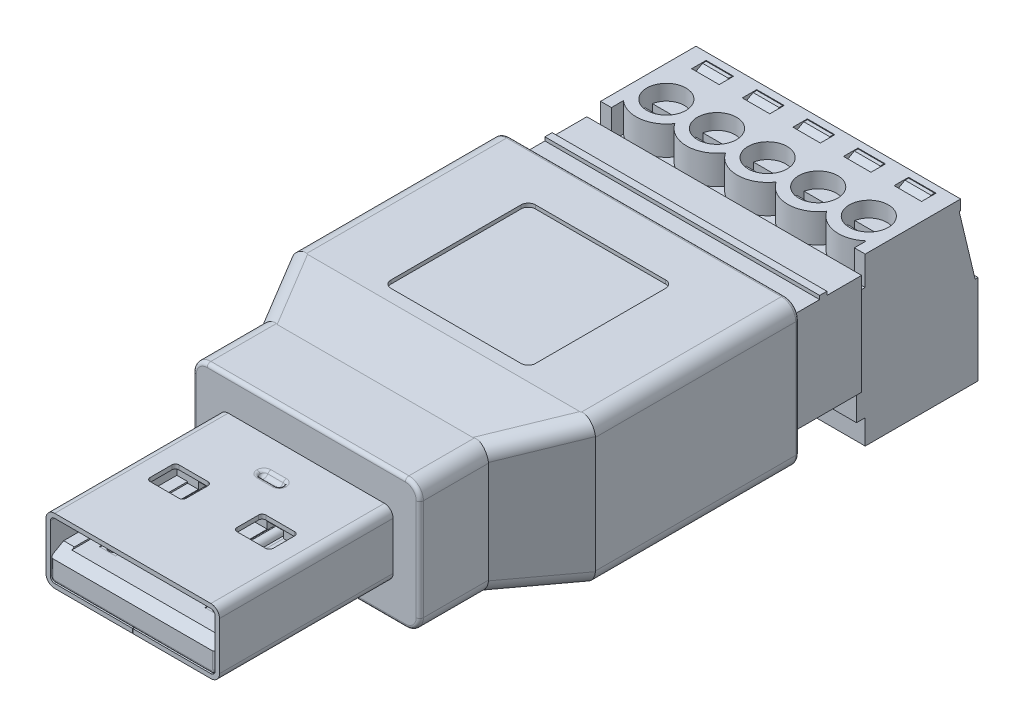
SolidWorks part; units mm, degrees
ref_plane "Front Plane" through (0, 0, 0) normal (0, 0, 1) x (1, 0, 0)
ref_plane "Top Plane" through (0, 0, 0) normal (0, 1, 0) x (1, 0, 0)
ref_plane "Right Plane" through (0, 0, 0) normal (1, 0, 0) x (0, 0, -1)
sketch "Sketch1" plane through (0, 0, 0) normal (1, 0, 0) x (0, 0, -1)
  line L0 (-24.65, 0) -> (24.65, 0) construction
  line L1 (-12.65, 4.5) -> (-12.65, -4.5) construction
  line L2 (10.95, 5) -> (10.95, -5) construction
  line L3 (10.95, 5) -> (-3.15, 5) construction
  line L4 (-12.65, 4.5) -> (-7.9, 4.5) construction
  line L5 (-7.9, 4.5) -> (-3.15, 5) construction
  line L6 (-24.65, 2.25) -> (-24.65, -2.25) construction
  line L7 (16.25, 3.5) -> (16.25, -3.5) construction
  line L8 (24.65, 4.3) -> (24.65, -7.2) construction
  line L9 (24.65, -7.2) -> (16.85, -7.2) construction
  line L10 (16.85, -7.2) -> (16.85, -5.5)
  line L11 (16.85, -5.5) -> (16.25, -5.5)
  line L12 (16.25, 2.3) -> (16.85, 2.3)
  line L13 (16.85, 2.3) -> (16.85, 4.3)
  line L14 (16.85, 4.3) -> (23.45, 4.3)
  line L15 (24.65, -1) -> (24.45, -1) construction
  line L16 (23.45, 4.3) -> (23.45, 3.6) construction
  line L17 (23.45, 3.6) -> (24.45, -1) construction
  point P3 (10.95, 0)
  point P4 (-12.65, 0)
  point P20 (24.65, 0.5781)
  dimension "USB Length" = 12
  dimension "Rear Connector Length" = 13.7
  dimension "USB Housing Length" = 23.6
  dimension "D1" = 9
  dimension "D2" = 10
  dimension "D3" = 4.75
  dimension "D4" = 9.5
  dimension "D5" = 4.5
  dimension "D6" = 7
  dimension "D7" = 5.3
  dimension "D8" = 11.5
  dimension "D9" = 0.8
  dimension "D11" = 37.3
  dimension "D12" = 7.8
  dimension "D13" = 1.7
  dimension "D10" = 2
  dimension "D14" = 6.6
  dimension "D15" = 7.7781
  dimension "D16" = 6.2
  dimension "D17" = 0.2
  dimension "D18" = 0.7
sketch "Sketch2" plane through (0, 0, 0) normal (0, 1, 0) x (1, 0, 0)
  line L0 (-10.5, 10.95) -> (10.5, 10.95)
  line L1 (-7.85, -12.65) -> (7.85, -12.65)
  line L2 (-7.85, -12.65) -> (-7.85, -7.9)
  line L3 (-7.85, -7.9) -> (-10.5, -3.15)
  line L4 (-10.5, -3.15) -> (-10.5, 10.95)
  line L5 (-6, -24.65) -> (6, -24.65)
  line L6 (-4.25, -17.7) -> (-4.25, -19.2)
  line L7 (-4, -17.45) -> (-2, -17.45)
  line L8 (-4, -19.45) -> (-2, -19.45)
  line L9 (-1.75, -17.7) -> (-1.75, -19.2)
  line L10 (0, -12.65) -> (0, -24.65) construction
  line L11 (0, -12.65) -> (0, -17.45) construction
  line L12 (-0.5, -15.05) -> (0.5, -15.05) construction
  line L13 (-0.5, -14.55) -> (0.5, -14.55)
  line L14 (-0.5, -15.55) -> (0.5, -15.55)
  line L15 (-9.5, 10.95) -> (-9.5, 16.25) construction
  line L16 (-9.5, 13.85) -> (-9.5, 13.35)
  line L17 (-9.5, 13.85) -> (9.5, 13.85)
  line L18 (-9.5, 13.35) -> (9.5, 13.35)
  line L19 (9.5, 13.85) -> (9.5, 13.35)
  line L20 (-9.15, 16.25) -> (-9.15, 24.65) construction
  line L21 (-9.15, 17.25) -> (9.15, 17.25) construction
  line L22 (0, 17.25) -> (0, 16.25) construction
  line L23 (0, -24.65) -> (0, 24.65) construction
  line L24 (-4.5, 7.7) -> (4.5, 7.7)
  line L25 (-5, 7.2) -> (-5, -1.8)
  line L26 (5, 7.2) -> (5, -1.8)
  line L27 (-4.5, -2.3) -> (4.5, -2.3)
  line L28 (-5.25, 0.8981) -> (-2.6598, -2.15) construction
  line L29 (-4.6785, 1.3838) -> (-2.0883, -1.6643) construction
  line L30 (-5.8215, 0.4124) -> (-3.2313, -2.6357) construction
  line L31 (-10.5, -3.15) -> (10.5, -3.15) construction
  line L32 (-7.5, 8.95) -> (7.5, 8.95) construction
  line L33 (-7.5, 8.95) -> (-7.5, -3.15) construction
  line L34 (-6.75, 8.2) -> (2.0451, -2.15) construction
  line L35 (-6.1785, 8.6857) -> (2.6166, -1.6643) construction
  line L36 (-7.3215, 7.7143) -> (1.4736, -2.6357) construction
  line L37 (7.5, 8.95) -> (7.5, -3.15) construction
  line L38 (-2.0451, 8.2) -> (6.75, -2.15) construction
  line L39 (-1.4736, 8.6857) -> (7.3215, -1.6643) construction
  line L40 (-2.6166, 7.7143) -> (6.1785, -2.6357) construction
  line L41 (2.6598, 8.2) -> (5.25, 5.1519) construction
  line L42 (3.2313, 8.6857) -> (5.8215, 5.6376) construction
  line L43 (2.0883, 7.7143) -> (4.6785, 4.6662) construction
  line L44 (-3.3834, -0.1403) -> (-1.7944, 1.21) construction
  line L45 (-1.7809, 3.5107) -> (-0.1919, 4.861) construction
  line L46 (3.3834, 6.1903) -> (1.7944, 4.84) construction
  line L47 (-3.65, -22.3) -> (-3.65, -13) construction
  line L48 (-4, -22.3) -> (-4, -13)
  line L49 (-3.3, -22.3) -> (-3.3, -13)
  line L50 (-1.11, -21.3) -> (-1.11, -13) construction
  line L51 (-1.46, -21.3) -> (-1.46, -13)
  line L52 (-0.76, -21.3) -> (-0.76, -13)
  arc A0 (-4.25, -19.2) -> (-4, -19.45) centre (-4, -19.2) ccw
  arc A1 (-4, -17.45) -> (-4.25, -17.7) centre (-4, -17.7) ccw
  arc A2 (-2, -17.45) -> (-1.75, -17.7) centre (-2, -17.7) cw
  arc A3 (-2, -19.45) -> (-1.75, -19.2) centre (-2, -19.2) ccw
  arc A4 (-0.5, -14.55) -> (-0.5, -15.55) centre (-0.5, -15.05) ccw
  arc A5 (0.5, -15.55) -> (0.5, -14.55) centre (0.5, -15.05) ccw
  circle A6 centre (-7, 19.25) radius 1.35
  circle A8 centre (-3.5, 19.25) radius 1.35
  circle A9 centre (0, 19.25) radius 1.35
  circle A10 centre (3.5, 19.25) radius 1.35
  circle A11 centre (7, 19.25) radius 1.35
  arc A12 (5, -1.8) -> (4.5, -2.3) centre (4.5, -1.8) cw
  arc A13 (-5, -1.8) -> (-4.5, -2.3) centre (-4.5, -1.8) ccw
  arc A14 (-5, 7.2) -> (-4.5, 7.7) centre (-4.5, 7.2) cw
  arc A15 (4.5, 7.7) -> (5, 7.2) centre (4.5, 7.2) cw
  arc A16 (-4.6785, 1.3838) -> (-5.8215, 0.4124) centre (-5.25, 0.8981) ccw construction
  arc A17 (-3.2313, -2.6357) -> (-2.0883, -1.6643) centre (-2.6598, -2.15) ccw construction
  arc A18 (-6.1785, 8.6857) -> (-7.3215, 7.7143) centre (-6.75, 8.2) ccw construction
  arc A19 (1.4736, -2.6357) -> (2.6166, -1.6643) centre (2.0451, -2.15) ccw construction
  arc A20 (-1.4736, 8.6857) -> (-2.6166, 7.7143) centre (-2.0451, 8.2) ccw construction
  arc A21 (6.1785, -2.6357) -> (7.3215, -1.6643) centre (6.75, -2.15) ccw construction
  arc A22 (3.2313, 8.6857) -> (2.0883, 7.7143) centre (2.6598, 8.2) ccw construction
  arc A23 (4.6785, 4.6662) -> (5.8215, 5.6376) centre (5.25, 5.1519) ccw construction
  arc A24 (-4, -22.3) -> (-3.3, -22.3) centre (-3.65, -22.3) ccw
  arc A25 (-3.3, -13) -> (-4, -13) centre (-3.65, -13) ccw
  arc A26 (-1.46, -21.3) -> (-0.76, -21.3) centre (-1.11, -21.3) ccw
  arc A27 (-0.76, -13) -> (-1.46, -13) centre (-1.11, -13) ccw
  point P5 (-3, -19.45)
  point P24 (-4.25, -17.45)
  point P27 (-1.75, -17.45)
  point P30 (0, -15.05)
  point P38 (-9.5, 13.6)
  point P39 (-9.5, 13.6)
  point P60 (0, 7.7)
  point P67 (-3.9549, -0.6259)
  point P76 (-5, -2.3)
  point P79 (-5, 7.7)
  point P88 (-2.3525, 3.025)
  point P92 (-3.3834, -0.1403)
  point P103 (2.3525, 3.025)
  point P108 (3.9549, 6.6759)
  point P121 (-3.65, -17.65)
  point P130 (-1.11, -17.15)
  dimension "D7" = 0.25
  dimension "D16" = 2.7
  dimension "D21" = 0.5
  dimension "D1" = 21
  dimension "D2" = 15.7
  dimension "D3" = 12
  dimension "D4" = 2.5
  dimension "D5" = 2
  dimension "D6" = 3.5
  dimension "D8" = 5.2
  dimension "D9" = 1
  dimension "D10" = 1
  dimension "D11" = 19
  dimension "D12" = 0.5
  dimension "D13" = 18.3
  dimension "D14" = 3
  dimension "D15" = 1
  dimension "D17" = 7
  dimension "D19" = 10
  dimension "D20" = 3.25
  dimension "D23" = 5.5
  dimension "D24" = 1.5
  dimension "D25" = 0.25
  dimension "D27" = 2
  dimension "D28" = 3
  dimension "D22" = 1
  dimension "D26" = 2.54
  dimension "D29" = 0.7
  dimension "D30" = 2.22
  dimension "D31" = 2
  dimension "D18" = 5
sketch "Sketch3" plane through (0, 0, 0) normal (0, 0, 1) x (1, 0, 0)
  line L0 (-8.25, -1.85) -> (-8.25, -5.85)
  line L1 (-8.25, -1.85) -> (-5.75, -1.85)
  line L2 (-8.25, -5.85) -> (-5.75, -5.85)
  line L3 (-5.75, -1.85) -> (-5.75, -5.85)
  line L4 (-7, -1.85) -> (-7, 0) construction
  dimension "D1" = 1.35
  dimension "D2" = 4
  dimension "D3" = 2.5
sketch "Sketch4" plane through (0, 0, 0) normal (0, 1, 0) x (1, 0, 0)
  line L0 (-10.5, 10.95) -> (10.5, 10.95) construction
  line L1 (-10.5, -3.15) -> (-10.5, 10.95) construction
  line L2 (-7.85, -7.9) -> (-10.5, -3.15) construction
  line L3 (-7.85, -12.65) -> (-7.85, -7.9) construction
  line L4 (-7.85, -12.65) -> (7.85, -12.65) construction
  line L5 (-10.5, 10.95) -> (0, 10.95)
  line L6 (-10.5, -3.15) -> (-10.5, 10.95)
  line L7 (-7.85, -7.9) -> (-10.5, -3.15)
  line L8 (-7.85, -12.65) -> (-7.85, -7.9)
  line L9 (-7.85, -12.65) -> (0, -12.65)
  line L10 (0, 10.95) -> (0, -12.65)
extrude "Boss-Extrude1" add sketch "Sketch4" against normal up to vertex (5 mm away) from vertex up to point (0, -5, -10.95) starting at point (0, 5, -10.95)
sketch "Sketch5" plane through (0, 0, 0) normal (1, 0, 0) x (0, 0, -1)
  line L0 (-12.65, 4.5) -> (-7.9, 4.5) construction
  line L1 (-7.9, 4.5) -> (-3.15, 5) construction
  line L2 (-12.65, 4.5) -> (-7.9, 4.5)
  line L3 (-7.9, 4.5) -> (-3.15, 5)
  line L4 (-12.65, 4.5) -> (-12.65, -4.5)
  line L5 (-12.65, 0) -> (-17.4, 0) construction
  line L6 (-7.9, -4.5) -> (-3.15, -5)
  line L7 (-12.65, -4.5) -> (-7.9, -4.5)
extrude "Cut-Extrude1" cut sketch "Sketch5" against normal through all and the other way through all flip side to cut
sketch "Sketch7" plane through (0, 0, 0) normal (1, 0, 0) x (0, 0, -1)
  line L0 (10.95, 3.5) -> (13.35, 3.5)
  line L1 (10.95, 3.5) -> (10.95, -3.5)
  line L2 (16.25, 3.5) -> (16.25, -3.5)
  line L3 (10.95, -3.5) -> (16.25, -3.5)
  line L4 (16.25, 3.5) -> (16.25, -3.5) construction
  line L5 (10.95, 5) -> (10.95, -5) construction
  line L6 (13.35, 3.5) -> (13.35, 3.75)
  line L7 (13.35, 3.75) -> (13.85, 3.75)
  line L8 (13.85, 3.75) -> (13.85, 3.5)
  line L9 (13.85, 3.5) -> (16.25, 3.5)
  dimension "D1" = 0.25
extrude "Boss-Extrude2" add sketch "Sketch7" against normal up to vertex (9.5 mm away) separate body up to point (-9.5, 0, -10.95)
sketch "Sketch8" plane through (0, 0, 0) normal (1, 0, 0) x (0, 0, -1)
  line L0 (16.85, -5.5) -> (16.25, -5.5) construction
  line L1 (16.85, -7.2) -> (16.85, -5.5) construction
  line L2 (24.65, -7.2) -> (16.85, -7.2) construction
  line L3 (24.65, 4.3) -> (24.65, -7.2) construction
  line L4 (24.65, -1) -> (24.45, -1) construction
  line L6 (23.45, 4.3) -> (23.45, 3.6) construction
  line L7 (16.85, 4.3) -> (23.45, 4.3) construction
  line L8 (16.85, 2.3) -> (16.85, 4.3) construction
  line L9 (16.25, 2.3) -> (16.85, 2.3) construction
  line L10 (16.85, -5.5) -> (16.25, -5.5)
  line L11 (16.85, -7.2) -> (16.85, -5.5)
  line L12 (24.65, -7.2) -> (16.85, -7.2)
  line L13 (24.65, -1) -> (24.65, -7.2)
  line L14 (24.65, -1) -> (24.45, -1)
  line L16 (23.45, 4.3) -> (23.45, 3.6)
  line L17 (16.85, 4.3) -> (23.45, 4.3)
  line L18 (16.85, 2.3) -> (16.85, 4.3)
  line L19 (16.25, 2.3) -> (16.85, 2.3)
  line L20 (16.25, 2.3) -> (16.25, -5.5)
  line L21 (23.45, 3.6) -> (23.35, 3.6)
  line L22 (23.35, 3.6) -> (24.45, -1)
  dimension "D1" = 0.1
extrude "Boss-Extrude3" add sketch "Sketch8" against normal up to vertex (9.15 mm away) separate body up to point (-9.15, 0, -24.65)
sketch "Sketch9" plane through (0, 4.3, 0) normal (0, 1, 0) x (1, 0, 0)
  line L0 (-7.95, 22.95) -> (-6.05, 22.95)
  line L1 (-7.95, 22.95) -> (-7.95, 21.95)
  line L2 (-6.05, 22.95) -> (-6.05, 21.95)
  line L3 (-7.95, 21.95) -> (-6.05, 21.95)
  line L4 (-9.15, 23.45) -> (0, 23.45) construction
  line L5 (-4.45, 22.95) -> (-4.45, 21.95)
  line L6 (-4.45, 22.95) -> (-2.55, 22.95)
  line L7 (-4.45, 21.95) -> (-2.55, 21.95)
  line L8 (-2.55, 22.95) -> (-2.55, 21.95)
  line L9 (-0.95, 22.95) -> (-0.95, 21.95)
  line L10 (-0.95, 22.95) -> (0.95, 22.95)
  line L11 (-0.95, 21.95) -> (0.95, 21.95)
  line L12 (0.95, 22.95) -> (0.95, 21.95)
  circle A0 centre (0, 19.25) radius 1.35 construction
  circle A1 centre (-3.5, 19.25) radius 1.35 construction
  circle A2 centre (-7, 19.25) radius 1.35 construction
  circle A3 centre (0, 19.25) radius 1.35
  circle A4 centre (-3.5, 19.25) radius 1.35
  circle A5 centre (-7, 19.25) radius 1.35
  point P15 (-7, 21.95)
  point P16 (-3.5, 21.95)
  point P23 (0, 21.95)
  dimension "D1" = 0.5
  dimension "D2" = 1
  dimension "D3" = 1.9
extrude "Cut-Extrude2" cut sketch "Sketch9" against normal up to surface (2 mm away) up to face at (-4.575, 2.3, -16.55)
sketch "Sketch10" plane through (0, 4.3, 0) normal (0, 1, 0) x (1, 0, 0)
  line L0 (-8.4, 17.6848) -> (-8.4, 16.85)
  line L1 (-9.15, 16.85) -> (0, 16.85) construction
  line L2 (-8.4, 16.85) -> (0, 16.85)
  line L3 (0, 16.85) -> (0, 17.15)
  line L4 (-9.15, 23.45) -> (-9.15, 16.85) construction
  arc A0 (-8.4, 17.6848) -> (-5.25, 18.0892) centre (-7, 19.25) ccw
  circle A1 centre (-7, 19.25) radius 1.35 construction
  arc A3 (-1.75, 18.0892) -> (0, 17.15) centre (0, 19.25) ccw
  arc A4 (-5.25, 18.0892) -> (-1.75, 18.0892) centre (-3.5, 19.25) ccw
  circle A5 centre (-3.5, 19.25) radius 1.35 construction
  dimension "D1" = 0.75
  dimension "D2" = 0.75
extrude "Cut-Extrude3" cut sketch "Sketch10" against normal up to surface (2 mm away) up to face at (-4.575, 2.3, -16.55)
sketch "Sketch12" plane through (0, 0, 0) normal (1, 0, 0) x (0, 0, -1)
  line L0 (22.9, 4.3) -> (22.9, 3.3)
  line L1 (22.9, 3.3) -> (22.95, 3.3)
  line L2 (22.95, 2.3) -> (22.95, 4.3) construction
  line L3 (22.95, 3.3) -> (22.95, 2.3)
  line L4 (22.95, 2.3) -> (21.95, 2.3)
  line L5 (21.95, 2.3) -> (21.95, 3.6)
  line L6 (21.95, 4.3) -> (21.95, 2.3) construction
  line L7 (21.95, 3.6) -> (22.2, 3.6)
  line L8 (22.2, 3.6) -> (22.2, 4.0402)
  line L9 (22.2, 4.0402) -> (22.65, 4.3)
  line L10 (22.65, 4.3) -> (22.9, 4.3)
  line L11 (21.95, 4.3) -> (20.6, 4.3) construction
  line L12 (23.45, 4.3) -> (22.95, 4.3) construction
  dimension "D1" = 0.05
  dimension "D2" = 0.7
  dimension "D3" = 60
  dimension "D4" = 0.25
  dimension "D5" = 0.25
extrude "Boss-Extrude4" add sketch "Sketch12" against normal up to surface (7.95 mm away) up to face at (-7.95, 3.3, -22.45)
sketch "Sketch13" plane through (0, 3.6, 0) normal (0, 1, 0) x (1, 0, 0)
  line L0 (-7.95, 22.95) -> (-7.95, 21.95)
  line L1 (-7.95, 22.95) -> (-7.9, 22.95)
  line L2 (-7.95, 21.95) -> (-7.9, 21.95)
  line L3 (-7.9, 22.95) -> (-7.9, 21.95)
  line L4 (-6.05, 22.95) -> (-6.05, 21.95)
  line L5 (-6.05, 22.95) -> (-6.1, 22.95)
  line L6 (-6.05, 21.95) -> (-6.1, 21.95)
  line L7 (-6.1, 22.95) -> (-6.1, 21.95)
  line L8 (-7.95, 22.95) -> (-7.95, 22.9) construction
  line L9 (-4.45, 22.95) -> (-4.45, 21.95)
  line L10 (-4.45, 22.95) -> (-4.4, 22.95)
  line L11 (-4.45, 21.95) -> (-4.4, 21.95)
  line L12 (-4.4, 22.95) -> (-4.4, 21.95)
  line L13 (-2.55, 21.95) -> (-2.55, 22.95)
  line L14 (-2.55, 21.95) -> (-2.6, 21.95)
  line L15 (-2.55, 22.95) -> (-2.6, 22.95)
  line L16 (-2.6, 21.95) -> (-2.6, 22.95)
  line L17 (-0.95, 22.95) -> (-0.95, 21.95)
  line L18 (-0.95, 22.95) -> (-0.9, 22.95)
  line L19 (-0.95, 21.95) -> (-0.9, 21.95)
  line L20 (-0.9, 22.95) -> (-0.9, 21.95)
extrude "Cut-Extrude4" cut sketch "Sketch13" along normal blind 10
sketch "Sketch15" plane through (0, 0, -24.65) normal (0, 0, -1) x (-1, 0, 0)
  line L0 (8.25, -1.85) -> (5.75, -1.85) construction
  line L1 (8.25, -1.85) -> (8.25, -5.85) construction
  line L2 (8.25, -5.85) -> (5.75, -5.85) construction
  line L3 (5.75, -1.85) -> (5.75, -5.85) construction
  line L4 (8.25, -1.85) -> (5.75, -1.85)
  line L5 (8.25, -1.85) -> (8.25, -5.85)
  line L6 (8.25, -5.85) -> (5.75, -5.85)
  line L7 (5.75, -1.85) -> (5.75, -5.85)
  line L8 (2.25, -1.85) -> (2.25, -5.85)
  line L9 (4.75, -1.85) -> (2.25, -1.85)
  line L10 (4.75, -1.85) -> (4.75, -5.85)
  line L11 (4.75, -5.85) -> (2.25, -5.85)
  line L12 (-1.25, -1.85) -> (-1.25, -5.85)
  line L13 (1.25, -1.85) -> (-1.25, -1.85)
  line L14 (1.25, -1.85) -> (1.25, -5.85)
  line L15 (1.25, -5.85) -> (-1.25, -5.85)
  line L19 (0, -1.85) -> (0, 4.3) construction
  dimension "D1" = 3
extrude "Cut-Extrude5" cut sketch "Sketch15" against normal blind 2
draft "Draft1" type of draft neutral plane draft angle 5 faces to draft 8 face at (-0.625, -5.85, -23.65) face at (-3.5, -5.85, -23.65) face at (-2.25, -3.85, -23.65) face at (-1.25, -3.85, -23.65) face at (-4.75, -3.85, -23.65) face at (-7, -5.85, -23.65) face at (-8.25, -3.85, -23.65) face at (-5.75, -3.85, -23.65) neutral plane through (-9.15, -1, -24.65) neutral plane normal (0, 0, -1) parameters "D1"=5
draft "Draft2" type of draft neutral plane draft angle 30 faces to draft 3 face at (-0.5813, -1.85, -23.65) face at (-3.5, -1.85, -23.65) face at (-7, -1.85, -23.65) neutral plane through (-9.15, -1, -24.65) neutral plane normal (0, 0, -1) parameters "D1"=30
sketch "Sketch16" plane through (0, 0, -22.65) normal (0, 0, -1) x (-1, 0, 0)
  line L4 (0, -7.2) -> (0, -5.85) construction
  line L12 (8.575, -6.175) -> (8.575, -2.5047)
  line L13 (8.575, -2.5047) -> (5.425, -2.5047)
  line L14 (5.425, -2.5047) -> (5.425, -6.175)
  line L15 (5.425, -6.175) -> (8.575, -6.175)
  line L16 (8.575, -6.175) -> (8.575, -2.5047)
  line L17 (8.575, -2.5047) -> (0, -2.5047)
  line L18 (0, -2.5047) -> (0, -6.175)
  line L19 (0, -6.175) -> (8.575, -6.175)
  dimension "D1" = 0.5
extrude "Cut-Extrude6" cut sketch "Sketch16" against normal blind 2
sketch "Sketch17" plane through (-8.575, 0, 0) normal (1, 0, 0) x (0, 0, -1)
  line L0 (22.65, -3.3047) -> (22.65, -2.5047)
  line L1 (22.65, -3.3047) -> (22.25, -3.3047)
  line L2 (22.65, -2.5047) -> (22.25, -2.5047)
  line L3 (22.25, -3.3047) -> (22.25, -2.5047)
  line L4 (22.65, -2.5047) -> (22.65, -3.0047) construction
  line L5 (20.65, -2.5047) -> (22.65, -2.5047) construction
  dimension "D1" = 0.4
  dimension "D2" = 0.3
extrude "Boss-Extrude5" add sketch "Sketch17" along normal up to surface (8.575 mm away) separate body up to face at (0, 0.2273, -21.3742)
sketch "Sketch18" plane through (0, -7.2, 0) normal (0, -1, 0) x (1, 0, 0)
  line L0 (-6.05, -24.05) -> (-7.95, -24.05)
  line L1 (-6.05, -24.05) -> (-6.05, -23.05)
  line L2 (-7.95, -24.05) -> (-7.95, -23.05)
  line L3 (-6.05, -23.05) -> (-7.95, -23.05)
  line L4 (-7.95, -22.95) -> (-7.95, -21.95) construction
  line L5 (-6.05, -21.95) -> (-6.05, -22.95) construction
  line L6 (-9.15, -24.65) -> (0, -24.65) construction
  line L7 (-2.55, -24.05) -> (-2.55, -23.05)
  line L8 (-2.55, -24.05) -> (-4.45, -24.05)
  line L9 (-2.55, -23.05) -> (-4.45, -23.05)
  line L10 (-4.45, -24.05) -> (-4.45, -23.05)
  line L11 (0.95, -24.05) -> (0.95, -23.05)
  line L12 (0.95, -24.05) -> (-0.95, -24.05)
  line L13 (0.95, -23.05) -> (-0.95, -23.05)
  line L14 (-0.95, -24.05) -> (-0.95, -23.05)
  line L15 (-3.5, -24.05) -> (-3.5, -24.65) construction
  line L16 (-4.75, -24.65) -> (-2.25, -24.65) construction
  dimension "D1" = 0.6
  dimension "D2" = 3
extrude "Cut-Extrude7" cut sketch "Sketch18" against normal blind 1
sketch "Sketch19" plane through (0, 0, 0) normal (1, 0, 0) x (0, 0, -1)
  line L0 (23.05, -6.7) -> (23.3335, -6.7)
  line L1 (23.05, -6.2) -> (23.05, -7.2) construction
  line L2 (23.3335, -6.7) -> (23.7665, -6.95)
  line L3 (23.7665, -6.95) -> (24.05, -6.95)
  line L4 (24.05, -7.2) -> (24.05, -6.2) construction
  line L5 (23.05, -7.2) -> (24.05, -7.2) construction
  line L6 (23.05, -6.7) -> (23.05, -6.2)
  line L7 (23.05, -6.2) -> (24.05, -6.2)
  line L8 (24.05, -6.2) -> (24.05, -6.95)
  dimension "D1" = 0.25
  dimension "D2" = 0.25
  dimension "D3" = 210
extrude "Boss-Extrude6" add sketch "Sketch19" against normal up to surface (7.95 mm away) up to face at (-7.95, -6.7, -23.55)
sketch "Sketch20" plane through (0, -6.7, 0) normal (0, -1, 0) x (1, 0, 0)
  line L0 (-7.95, -23.05) -> (-7.95, -24.05)
  line L1 (-7.95, -23.05) -> (-7.9, -23.05)
  line L2 (-7.95, -24.05) -> (-7.9, -24.05)
  line L3 (-7.9, -23.05) -> (-7.9, -24.05)
  line L4 (-6.05, -23.05) -> (-6.05, -24.05)
  line L5 (-6.05, -23.05) -> (-6.1, -23.05)
  line L6 (-6.05, -24.05) -> (-6.1, -24.05)
  line L7 (-6.1, -23.05) -> (-6.1, -24.05)
  line L8 (-4.45, -23.05) -> (-4.45, -24.05)
  line L9 (-4.45, -23.05) -> (-4.4, -23.05)
  line L10 (-4.45, -24.05) -> (-4.4, -24.05)
  line L11 (-4.4, -23.05) -> (-4.4, -24.05)
  line L12 (-2.55, -23.05) -> (-2.55, -24.05)
  line L13 (-2.55, -23.05) -> (-2.6, -23.05)
  line L14 (-2.55, -24.05) -> (-2.6, -24.05)
  line L15 (-2.6, -23.05) -> (-2.6, -24.05)
  line L16 (-0.95, -23.05) -> (-0.95, -24.05)
  line L17 (-0.95, -23.05) -> (-0.9, -23.05)
  line L18 (-0.95, -24.05) -> (-0.9, -24.05)
  line L19 (-0.9, -23.05) -> (-0.9, -24.05)
  line L20 (-7.9, -22.9) -> (-7.9, -22.65) construction
extrude "Cut-Extrude8" cut sketch "Sketch20" along normal blind 1 and the other way blind 0.5
sketch "Sketch21" plane through (0, -5.5, 0) normal (0, -1, 0) x (1, 0, 0)
  line L0 (-2.1, -16.25) -> (-2.1, -16.85)
  line L1 (-2.1, -16.25) -> (-1.4, -16.25)
  line L2 (-2.1, -16.85) -> (-1.4, -16.85)
  line L3 (-1.4, -16.25) -> (-1.4, -16.85)
  line L4 (-9.15, -16.25) -> (0, -16.25) construction
  line L5 (-9.15, -16.85) -> (0, -16.85) construction
  line L6 (-5.6, -16.25) -> (-5.6, -16.85)
  line L7 (-5.6, -16.25) -> (-4.9, -16.25)
  line L8 (-5.6, -16.85) -> (-4.9, -16.85)
  line L9 (-4.9, -16.25) -> (-4.9, -16.85)
  line L10 (-6.05, -23.05) -> (-4.45, -23.05) construction
  line L12 (-5.25, -16.85) -> (-5.25, -23.05) construction
  line L13 (-2.55, -23.05) -> (-0.95, -23.05) construction
  line L14 (-1.75, -16.85) -> (-1.75, -23.05) construction
  dimension "D1" = 0.7
extrude "Cut-Extrude9" cut sketch "Sketch21" against normal offset from surface (3 mm away) 1 up to face at (-4.75, -3.5, -13.6) offset beyond the face yes
sketch "Sketch23" plane through (0, 5, 0) normal (0, 1, 0) x (1, 0, 0)
  line L0 (-4.5, 7.7) -> (4.5, 7.7) construction
  line L1 (5, 7.2) -> (5, -1.8) construction
  line L2 (-4.5, -2.3) -> (4.5, -2.3) construction
  line L3 (-5, 7.2) -> (-5, -1.8) construction
  line L4 (-4.5, 7.7) -> (4.5, 7.7)
  line L5 (5, 7.2) -> (5, -1.8)
  line L6 (-4.5, -2.3) -> (4.5, -2.3)
  line L7 (-5, 7.2) -> (-5, -1.8)
  arc A0 (-4.5, 7.7) -> (-5, 7.2) centre (-4.5, 7.2) ccw construction
  arc A1 (5, 7.2) -> (4.5, 7.7) centre (4.5, 7.2) ccw construction
  arc A2 (4.5, -2.3) -> (5, -1.8) centre (4.5, -1.8) ccw construction
  arc A3 (-5, -1.8) -> (-4.5, -2.3) centre (-4.5, -1.8) ccw construction
  arc A4 (-4.5, 7.7) -> (-5, 7.2) centre (-4.5, 7.2) ccw
  arc A5 (5, 7.2) -> (4.5, 7.7) centre (4.5, 7.2) ccw
  arc A6 (4.5, -2.3) -> (5, -1.8) centre (4.5, -1.8) ccw
  arc A7 (-5, -1.8) -> (-4.5, -2.3) centre (-4.5, -1.8) ccw
extrude "Cut-Extrude10" cut sketch "Sketch23" against normal blind 0.25
fillet "Fillet1" radius 1 6 edges at (-7.85, -4.5, 10.275) (-9.175, -4.75, 5.525) (-10.5, -5, -3.9) (-10.5, 5, -3.9) (-9.175, 4.75, 5.525) (-7.85, 4.5, 10.275)
fillet "Fillet2" radius 0.25 10 edges at (-4.75, -5, -10.95) (-10.2071, -4.7071, -10.95) (-10.5, 0, -10.95) (-10.2071, 4.7071, -10.95) (-4.75, 5, -10.95) (-3.425, -4.5, 12.65) (-7.5571, -4.2071, 12.65) (-7.85, 0, 12.65) (-7.5571, 4.2071, 12.65) (-3.425, 4.5, 12.65)
sketch "Sketch24" plane through (0, 0, 12.65) normal (0, 0, 1) x (1, 0, 0)
  line L0 (5.4, 2.25) -> (-5.4, 2.25)
  line L1 (0, 2.25) -> (0, -2.25) construction
  line L2 (-6, 1.65) -> (-6, -1.65)
  line L3 (5.4, -2.25) -> (-5.4, -2.25)
  line L4 (0, -4.25) -> (0, 4.25) construction
  line L5 (6, 1.65) -> (6, -1.65)
  arc A0 (-6, -1.65) -> (-5.4, -2.25) centre (-5.4, -1.65) ccw
  arc A1 (-5.4, 2.25) -> (-6, 1.65) centre (-5.4, 1.65) ccw
  arc A2 (5.4, 2.25) -> (6, 1.65) centre (5.4, 1.65) cw
  arc A3 (6, -1.65) -> (5.4, -2.25) centre (5.4, -1.65) cw
  dimension "D1" = 0.6
extrude "Extrude-Thin1" add sketch "Sketch24" along normal up to vertex (12 mm away) separate body thin up to point (0, 0, 24.65) thin type one direction reverse wall 0.3
sketch "Sketch25" plane through (0, 2.25, 0) normal (0, -1, 0) x (-1, 0, 0)
  line L0 (-1.125, -15.05) -> (1.125, -15.05)
  line L1 (-1.125, -15.05) -> (-1.125, -15.056)
  line L2 (1.125, -15.05) -> (1.125, -15.056)
  line L3 (-0.531, -15.65) -> (0.531, -15.65)
  line L4 (1.75, -17.45) -> (1.75, -12.65) construction
  line L5 (4, -17.45) -> (2, -17.45) construction
  line L6 (1.75, -17.7) -> (1.75, -19.2) construction
  line L8 (5.4, -12.65) -> (-5.4, -12.65) construction
  arc A0 (1.125, -15.056) -> (0.531, -15.65) centre (0.531, -15.056) cw
  arc A1 (-1.125, -15.056) -> (-0.531, -15.65) centre (-0.531, -15.056) ccw
  point P7 (1.75, -15.05)
  point P8 (0, -15.05)
  dimension "D2" = 0.594
  dimension "D1" = 2.25
  dimension "D3" = 0.6
revolve "Revolve1" add sketch "Sketch25" angle 180 about L0 reverse direction yes
sketch "Sketch27" plane through (0, 2.25, 0) normal (0, 1, 0) x (1, 0, 0)
  line L0 (1.125, -15.05) -> (-1.125, -15.05) construction
  line L1 (0.8249, -15.05) -> (-0.8249, -15.05)
  line L8 (-0.531, -15.35) -> (0.531, -15.35)
  line L9 (-0.531, -15.35) -> (0.531, -15.35)
  arc A8 (-0.825, -15.056) -> (-0.531, -15.35) centre (-0.531, -15.056) ccw
  arc A9 (0.531, -15.35) -> (0.825, -15.056) centre (0.531, -15.056) ccw
  arc A10 (-0.8249, -15.05) -> (-0.531, -15.35) centre (-0.531, -15.056) ccw
  arc A11 (0.531, -15.35) -> (0.8249, -15.05) centre (0.531, -15.056) ccw
  dimension "D1" = 0.3
revolve "Cut-Revolve1" cut sketch "Sketch27" angle 360 about L1
fillet "Fillet3" radius 0.25 6 edges at (0, 2.25, 15.35) (0.741, 2.25, 15.2618) (-0.741, 2.25, 15.2618) (0.741, 2.25, 14.8382) (-0.741, 2.25, 14.8382) (0, 2.25, 14.75)
sketch "Sketch28" plane through (0, 2.25, 0) normal (0, 1, 0) x (1, 0, 0)
  line L0 (-4, -17.45) -> (-2, -17.45) construction
  line L1 (-4.25, -17.7) -> (-4.25, -19.2) construction
  line L2 (-4, -19.45) -> (-2, -19.45) construction
  line L3 (-1.75, -17.7) -> (-1.75, -19.2) construction
  line L4 (-4, -17.45) -> (-2, -17.45)
  line L5 (-4.25, -17.7) -> (-4.25, -19.2)
  line L6 (-4, -19.45) -> (-2, -19.45)
  line L7 (-1.75, -17.7) -> (-1.75, -19.2)
  line L8 (0, -24.65) -> (0, -19.45) construction
  line L9 (5.4, -24.65) -> (-5.4, -24.65) construction
  line L10 (1.75, -17.7) -> (1.75, -19.2)
  line L11 (4, -19.45) -> (2, -19.45)
  line L12 (4.25, -17.7) -> (4.25, -19.2)
  line L13 (4, -17.45) -> (2, -17.45)
  arc A0 (-1.75, -17.7) -> (-2, -17.45) centre (-2, -17.7) ccw construction
  arc A1 (-4, -17.45) -> (-4.25, -17.7) centre (-4, -17.7) ccw construction
  arc A2 (-4.25, -19.2) -> (-4, -19.45) centre (-4, -19.2) ccw construction
  arc A3 (-2, -19.45) -> (-1.75, -19.2) centre (-2, -19.2) ccw construction
  arc A4 (-1.75, -17.7) -> (-2, -17.45) centre (-2, -17.7) ccw
  arc A5 (-4, -17.45) -> (-4.25, -17.7) centre (-4, -17.7) ccw
  arc A6 (-4.25, -19.2) -> (-4, -19.45) centre (-4, -19.2) ccw
  arc A7 (-2, -19.45) -> (-1.75, -19.2) centre (-2, -19.2) ccw
  arc A8 (2, -19.45) -> (1.75, -19.2) centre (2, -19.2) cw
  arc A9 (4.25, -19.2) -> (4, -19.45) centre (4, -19.2) cw
  arc A10 (4, -17.45) -> (4.25, -17.7) centre (4, -17.7) cw
  arc A11 (1.75, -17.7) -> (2, -17.45) centre (2, -17.7) cw
extrude "Cut-Extrude12" cut sketch "Sketch28" against normal through all
sketch "Sketch30" plane through (0, -2.25, 0) normal (0, -1, 0) x (1, 0, 0)
  line L0 (1, 24.65) -> (1, 22.7364) construction
  line L1 (1.3355, 22.5015) -> (1.8827, 22.7006) construction
  line L2 (2.2182, 22.4657) -> (2.2182, 20.4657) construction
  line L3 (1.8827, 20.2308) -> (1.3355, 20.43) construction
  line L4 (1.3355, 14.0701) -> (1.8827, 14.2693) construction
  line L5 (2.2182, 14.0344) -> (2.2182, 12.0344) construction
  line L6 (1.8827, 11.7995) -> (1.3355, 11.9986) construction
  line L7 (1, 20.195) -> (1, 14.3051) construction
  line L8 (1, 11.7637) -> (1, 9.8501) construction
  line L9 (1, 14.3051) -> (1, 13.0344) construction
  line L10 (1, 13.0344) -> (1, 11.7637) construction
  line L11 (1, 13.0344) -> (2.2182, 13.0344) construction
  line L12 (0.5, 24.65) -> (0.5, 23.8393) construction
  line L13 (0, 11.7637) -> (0, 9.8501)
  line L14 (-0.8827, 11.7995) -> (-0.3355, 11.9986)
  line L15 (-1.2182, 14.0344) -> (-1.2182, 12.0344)
  line L16 (-5.4, 24.65) -> (5.4, 24.65) construction
  line L17 (-0.3355, 14.0701) -> (-0.8827, 14.2693)
  line L18 (0, 20.195) -> (0, 14.3051)
  line L19 (-0.8827, 20.2308) -> (-0.3355, 20.43)
  line L20 (-1.2182, 22.4657) -> (-1.2182, 20.4657)
  line L21 (-0.3355, 22.5015) -> (-0.8827, 22.7006)
  line L22 (0, 24.65) -> (0, 22.7364)
  arc A0 (1.3355, 14.0701) -> (1, 14.3051) centre (1.25, 14.3051) cw construction
  arc A1 (1.3355, 11.9986) -> (1, 11.7637) centre (1.25, 11.7637) ccw construction
  arc A2 (1.3355, 22.5015) -> (1, 22.7364) centre (1.25, 22.7364) cw construction
  arc A3 (1.3355, 20.43) -> (1, 20.195) centre (1.25, 20.195) ccw construction
  arc A4 (1.8827, 22.7006) -> (2.2182, 22.4657) centre (1.9682, 22.4657) cw construction
  arc A5 (2.2182, 20.4657) -> (1.8827, 20.2308) centre (1.9682, 20.4657) cw construction
  arc A6 (1.8827, 14.2693) -> (2.2182, 14.0344) centre (1.9682, 14.0344) cw construction
  arc A7 (2.2182, 12.0344) -> (1.8827, 11.7995) centre (1.9682, 12.0344) cw construction
  arc A8 (-0.3355, 11.9986) -> (0, 11.7637) centre (-0.25, 11.7637) cw
  arc A9 (-1.2182, 12.0344) -> (-0.8827, 11.7995) centre (-0.9682, 12.0344) ccw
  arc A10 (-0.8827, 14.2693) -> (-1.2182, 14.0344) centre (-0.9682, 14.0344) ccw
  arc A11 (-0.3355, 14.0701) -> (0, 14.3051) centre (-0.25, 14.3051) ccw
  arc A12 (-0.3355, 20.43) -> (0, 20.195) centre (-0.25, 20.195) cw
  arc A13 (-1.2182, 20.4657) -> (-0.8827, 20.2308) centre (-0.9682, 20.4657) ccw
  arc A14 (-0.8827, 22.7006) -> (-1.2182, 22.4657) centre (-0.9682, 22.4657) ccw
  arc A15 (-0.3355, 22.5015) -> (0, 22.7364) centre (-0.25, 22.7364) ccw
  point P36 (2.2182, 21.4657)
  point P55 (0, 24.65)
  dimension "D1" = 0.25
  dimension "D2" = 8.4313
  dimension "D3" = 1.2182
  dimension "D4" = 70
  dimension "D5" = 2.5414
  dimension "D6" = 2
  dimension "D7" = 1.9136
  dimension "D8" = 1
  dimension "D9" = 0.5
extrude "Cut-Extrude-Thin1" cut sketch "Sketch30" against normal up to surface (0.3 mm away) thin up to face at (-3, -1.95, 18.45) thin type mid plane wall 0.02
sketch "Sketch31" plane through (0, 2.3, 0) normal (0, 1, 0) x (1, 0, 0)
  circle A0 centre (-7, 19.25) radius 1.25
  dimension "D1" = 2.5
extrude "Boss-Extrude7" add sketch "Sketch31" along normal offset from surface (1 mm away) 1 separate body up to face at (-3.5, 4.3, -17.9)
sketch "Sketch32" plane through (0, 3.3, 0) normal (0, 1, 0) x (1, 0, 0)
  line L0 (-8.35, 19.5) -> (-8.35, 19)
  line L1 (-8.35, 19.5) -> (-5.65, 19.5)
  line L2 (-8.35, 19) -> (-5.65, 19)
  line L3 (-5.65, 19.5) -> (-5.65, 19)
  line L4 (-7, 19.5) -> (-7, 19) construction
  circle A0 centre (-7, 19.25) radius 1.35 construction
  circle A1 centre (-7, 19.25) radius 1.25 construction
  point P8 (-7, 19.25)
  dimension "D1" = 0.5
extrude "Cut-Extrude13" cut sketch "Sketch32" against normal blind 0.5
pattern_linear "LPattern1" count 5 spacing 3.5 along (1, 0, 0) of bodies 128
sketch "Sketch34" plane through (0, 0, 0) normal (1, 0, 0) x (0, 0, -1)
  line L0 (-24.65, 0) -> (-24.65, -1.95)
  line L1 (-24.65, 0) -> (-15.9, 0)
  line L2 (-24.65, -1.95) -> (-12.65, -1.95)
  line L3 (-12.65, 1.95) -> (-12.65, -1.95)
  line L4 (-12.65, -1.65) -> (-12.65, 1.65) construction
  line L5 (-24.65, -1.65) -> (-24.65, 1.65) construction
  line L6 (-24.65, -1.95) -> (-12.65, -1.95) construction
  line L7 (-15.9, 0) -> (-15.9, 1.95)
  line L8 (-15.9, 1.95) -> (-12.65, 1.95)
  line L9 (-24.65, 1.95) -> (-12.65, 1.95) construction
  dimension "D1" = 1.95
  dimension "D2" = 8.75
extrude "Boss-Extrude8" add sketch "Sketch34" against normal up to surface and the other way up to surface separate body up to face at (-5.7, 0, 18.65) other way up to face at (5.7, 0, 18.65)
fillet "Fillet4" radius 0.3 2 edges at (-5.7, -1.95, 18.65) (5.7, -1.95, 18.65)
chamfer "Chamfer1" distance 0.53 angle 60 1 edges at (0, 0, 24.65) first distance on face at (0, -1.2207, 24.65)
sketch "Sketch35" plane through (0, 0, 0) normal (0, 1, 0) x (1, 0, 0)
  line L0 (-4.2125, -15.9) -> (-4.2125, -22.75)
  line L1 (-4.2125, -15.9) -> (-3.0875, -15.9)
  line L2 (-4.2125, -22.75) -> (-3.0875, -22.75)
  line L3 (4.2125, -15.9) -> (4.2125, -22.75)
  line L4 (-3.0875, -22.75) -> (-3.0875, -15.9)
  line L5 (-1.6725, -21.75) -> (-0.5475, -21.75)
  line L6 (3.0875, -15.9) -> (3.0875, -22.75)
  line L7 (3.0875, -22.75) -> (4.2125, -22.75)
  line L8 (-1.6725, -15.9) -> (-1.6725, -21.75)
  line L9 (-0.5475, -15.9) -> (-0.5475, -21.75)
  line L10 (-1.6725, -15.9) -> (-0.5475, -15.9)
  line L11 (0, -15.9) -> (0, -17.025) construction
  line L12 (1.6725, -15.9) -> (1.6725, -21.75)
  line L13 (1.6725, -21.75) -> (0.5475, -21.75)
  line L14 (0.5475, -15.9) -> (0.5475, -21.75)
  line L15 (3.0875, -15.9) -> (4.2125, -15.9)
  line L16 (0.5475, -15.9) -> (1.6725, -15.9)
  line L17 (5.4, -24.65) -> (-5.4, -24.65) construction
  line L18 (-5.7, -15.9) -> (5.7, -15.9) construction
  point P4 (0, -15.9)
  point P19 (-1.11, -21.75)
  point P20 (-3.65, -22.75)
  dimension "D1" = 1.125
  dimension "D2" = 1
  dimension "D3" = 2.54
  dimension "D4" = 1.11
  dimension "D5" = 1.9
extrude "Cut-Extrude14" cut sketch "Sketch35" against normal blind 0.15
sketch "Sketch36" plane through (0, -0.15, 0) normal (0, 1, 0) x (1, 0, 0)
  line L0 (-4.2125, -15.9) -> (-3.0875, -15.9)
  line L1 (-4.2125, -15.9) -> (-4.2125, -12.65)
  line L2 (-3.0875, -15.9) -> (-3.0875, -12.65)
  line L3 (-4.2125, -12.65) -> (-3.0875, -12.65)
  line L4 (-3.0875, -22.75) -> (-3.0875, -15.9) construction
  line L5 (5.4, -12.65) -> (-5.4, -12.65) construction
  line L6 (-1.6725, -15.9) -> (-0.5475, -15.9)
  line L7 (-1.6725, -15.9) -> (-1.6725, -12.65)
  line L8 (-0.5475, -15.9) -> (-0.5475, -12.65)
  line L9 (-1.6725, -12.65) -> (-0.5475, -12.65)
  line L14 (0, -15.9) -> (0, -17.025) construction
  line L15 (-0.5475, -15.9) -> (0.5475, -15.9) construction
  line L16 (1.6725, -12.65) -> (0.5475, -12.65)
  line L17 (0.5475, -15.9) -> (0.5475, -12.65)
  line L18 (1.6725, -15.9) -> (1.6725, -12.65)
  line L19 (1.6725, -15.9) -> (0.5475, -15.9)
  line L20 (4.2125, -12.65) -> (3.0875, -12.65)
  line L21 (3.0875, -15.9) -> (3.0875, -12.65)
  line L22 (4.2125, -15.9) -> (4.2125, -12.65)
  line L23 (4.2125, -15.9) -> (3.0875, -15.9)
extrude "Cut-Extrude15" cut sketch "Sketch36" along normal blind 0.525
sketch "Sketch37" plane through (0, -0.15, 0) normal (0, 1, 0) x (1, 0, 0)
  line L0 (-0.76, -21.3) -> (-0.76, -13) construction
  line L1 (-1.46, -21.3) -> (-1.46, -13) construction
  line L2 (-4, -22.3) -> (-4, -13) construction
  line L3 (-3.3, -22.3) -> (-3.3, -13) construction
  line L4 (-0.76, -21.3) -> (-0.76, -13)
  line L5 (-1.46, -21.3) -> (-1.46, -13)
  line L6 (-4, -22.3) -> (-4, -13)
  line L7 (-3.3, -22.3) -> (-3.3, -13)
  line L8 (0, -24.65) -> (0, -21.3) construction
  line L10 (3.3, -22.3) -> (3.3, -13)
  line L11 (4, -22.3) -> (4, -13)
  line L12 (1.46, -21.3) -> (1.46, -13)
  line L13 (0.76, -21.3) -> (0.76, -13)
  arc A0 (-1.46, -21.3) -> (-0.76, -21.3) centre (-1.11, -21.3) ccw construction
  arc A1 (-0.76, -13) -> (-1.46, -13) centre (-1.11, -13) ccw construction
  arc A2 (-4, -22.3) -> (-3.3, -22.3) centre (-3.65, -22.3) ccw construction
  arc A3 (-3.3, -13) -> (-4, -13) centre (-3.65, -13) ccw construction
  arc A4 (-1.46, -21.3) -> (-0.76, -21.3) centre (-1.11, -21.3) ccw
  arc A5 (-0.76, -13) -> (-1.46, -13) centre (-1.11, -13) ccw
  arc A6 (-4, -22.3) -> (-3.3, -22.3) centre (-3.65, -22.3) ccw
  arc A7 (-3.3, -13) -> (-4, -13) centre (-3.65, -13) ccw
  arc A8 (3.3, -13) -> (4, -13) centre (3.65, -13) cw
  arc A9 (4, -22.3) -> (3.3, -22.3) centre (3.65, -22.3) cw
  arc A10 (0.76, -13) -> (1.46, -13) centre (1.11, -13) cw
  arc A11 (1.46, -21.3) -> (0.76, -21.3) centre (1.11, -21.3) cw
extrude "Boss-Extrude9" add sketch "Sketch37" along normal blind 0.35 separate body
sketch "Sketch38" plane through (0, 0, 12.65) normal (0, 0, -1) x (-1, 0, 0)
  line L1 (4, 0.2) -> (3.3, 0.2) construction
  line L2 (0, 1.95) -> (0, 0) construction
  line L3 (5.7, 1.95) -> (-5.7, 1.95) construction
  line L4 (3.3, -0.15) -> (4, -0.15) construction
  line L5 (3.0875, -0.15) -> (4.2125, -0.15) construction
  line L6 (4, 0.2) -> (4, -0.15) construction
  line L7 (3.3, 0.2) -> (3.3, -0.15) construction
  line L9 (1.46, 0.2) -> (0.76, 0.2) construction
  line L10 (0.76, 0.2) -> (0.76, -0.15) construction
  line L11 (-3.3, -0.15) -> (-4, -0.15) construction
  circle A1 centre (3.65, -0.15) radius 0.35
  circle A2 centre (1.11, -0.15) radius 0.35
  circle A3 centre (-1.11, -0.15) radius 0.35
  circle A4 centre (-3.65, -0.15) radius 0.35
extrude "Cut-Extrude16" cut sketch "Sketch38" against normal through all flip side to cut
sketch "Sketch39" plane through (0, 0, 0) normal (1, 0, 0) x (0, 0, -1)
  line L0 (-12.65, 0.2) -> (-22.65, 0.2) construction
  line L1 (-22.65, 0.2) -> (-22.65, -0.15) construction
  line L2 (-22.3, 0.2) -> (-22.65, 0.2)
  line L3 (-22.65, 0.2) -> (-22.65, -0.15)
  arc A0 (-22.65, -0.15) -> (-22.3, 0.2) centre (-22.3, -0.15) cw
extrude "Cut-Extrude17" cut sketch "Sketch39" against normal through all both and the other way through all
sketch "Sketch40" plane through (0, 0, 0) normal (1, 0, 0) x (0, 0, -1)
  line L0 (-12.65, 0.2) -> (-21.65, 0.2) construction
  line L1 (-21.65, 0.2) -> (-21.65, -0.15) construction
  line L2 (-21.3, 0.2) -> (-21.65, 0.2)
  line L3 (-21.65, 0.2) -> (-21.65, -0.15)
  arc A0 (-21.65, -0.15) -> (-21.3, 0.2) centre (-21.3, -0.15) cw
extrude "Cut-Extrude18" cut sketch "Sketch40" against normal through all both and the other way through all
sketch "Sketch41" plane through (0, 0, 0) normal (0, 1, 0) x (1, 0, 0)
  line L0 (-4.9563, -24.65) -> (-4.9563, -15.9)
  line L1 (-4.9563, -24.65) -> (4.9563, -24.65)
  line L2 (-4.9563, -15.9) -> (4.9563, -15.9)
  line L3 (4.9563, -24.65) -> (4.9563, -15.9)
  line L4 (-5.7, -15.9) -> (-4.2125, -15.9) construction
  line L5 (4.2125, -15.9) -> (5.7, -15.9) construction
  line L6 (5.7, -24.65) -> (-5.7, -24.65) construction
  point P6 (-4.9563, -15.9)
extrude "Cut-Extrude19" cut sketch "Sketch41" against normal blind 0.1
fillet "Fillet5" radius 0.2 5 edges at (5.7, -1.09, 24.65) (5.6121, -1.8621, 24.65) (0, -1.95, 24.65) (-5.6121, -1.8621, 24.65) (-5.7, -1.09, 24.65)
mirror "Mirror1" about plane through (0, -5, -10.95) normal (1, 0, 0) of bodies 118 106 119 114
sketch "Sketch42" plane through (0, -5, 0) normal (0, -1, 0) x (1, 0, 0)
  line L0 (3.2313, -8.6857) -> (5.8215, -5.6376) construction
  line L1 (2.0883, -7.7143) -> (4.6785, -4.6662) construction
  line L2 (-2.6166, -7.7143) -> (6.1785, 2.6357) construction
  line L3 (-1.4736, -8.6857) -> (7.3215, 1.6643) construction
  line L4 (-5.8215, -0.4124) -> (-3.2313, 2.6357) construction
  line L5 (-4.6785, -1.3838) -> (-2.0883, 1.6643) construction
  line L6 (-7.3215, -7.7143) -> (1.4736, 2.6357) construction
  line L7 (-6.1785, -8.6857) -> (2.6166, 1.6643) construction
  line L8 (3.2313, -8.6857) -> (5.8215, -5.6376)
  line L9 (2.0883, -7.7143) -> (4.6785, -4.6662)
  line L10 (-2.6166, -7.7143) -> (6.1785, 2.6357)
  line L11 (-1.4736, -8.6857) -> (7.3215, 1.6643)
  line L12 (-5.8215, -0.4124) -> (-3.2313, 2.6357)
  line L13 (-4.6785, -1.3838) -> (-2.0883, 1.6643)
  line L14 (-7.3215, -7.7143) -> (1.4736, 2.6357)
  line L15 (-6.1785, -8.6857) -> (2.6166, 1.6643)
  arc A0 (2.0883, -7.7143) -> (3.2313, -8.6857) centre (2.6598, -8.2) ccw construction
  arc A1 (5.8215, -5.6376) -> (4.6785, -4.6662) centre (5.25, -5.1519) ccw construction
  arc A2 (-2.6166, -7.7143) -> (-1.4736, -8.6857) centre (-2.0451, -8.2) ccw construction
  arc A3 (7.3215, 1.6643) -> (6.1785, 2.6357) centre (6.75, 2.15) ccw construction
  arc A4 (-5.8215, -0.4124) -> (-4.6785, -1.3838) centre (-5.25, -0.8981) ccw construction
  arc A5 (-2.0883, 1.6643) -> (-3.2313, 2.6357) centre (-2.6598, 2.15) ccw construction
  arc A6 (-7.3215, -7.7143) -> (-6.1785, -8.6857) centre (-6.75, -8.2) ccw construction
  arc A7 (2.6166, 1.6643) -> (1.4736, 2.6357) centre (2.0451, 2.15) ccw construction
  arc A8 (2.0883, -7.7143) -> (3.2313, -8.6857) centre (2.6598, -8.2) ccw
  arc A9 (5.8215, -5.6376) -> (4.6785, -4.6662) centre (5.25, -5.1519) ccw
  arc A10 (-2.6166, -7.7143) -> (-1.4736, -8.6857) centre (-2.0451, -8.2) ccw
  arc A11 (7.3215, 1.6643) -> (6.1785, 2.6357) centre (6.75, 2.15) ccw
  arc A12 (-5.8215, -0.4124) -> (-4.6785, -1.3838) centre (-5.25, -0.8981) ccw
  arc A13 (-2.0883, 1.6643) -> (-3.2313, 2.6357) centre (-2.6598, 2.15) ccw
  arc A14 (-7.3215, -7.7143) -> (-6.1785, -8.6857) centre (-6.75, -8.2) ccw
  arc A15 (2.6166, 1.6643) -> (1.4736, 2.6357) centre (2.0451, 2.15) ccw
extrude "Cut-Extrude20" cut sketch "Sketch42" against normal blind 0.25
equation "\"D3@Sketch1\"=\"D4@Sketch1\"/2"
equation "\"D9@Sketch30\"=\"D8@Sketch30\"/2"
equation "\"D3@LPattern1\"=\"D17@Sketch2\"/2"
equation "\"D1@LPattern1\"=\"D18@Sketch2\""
